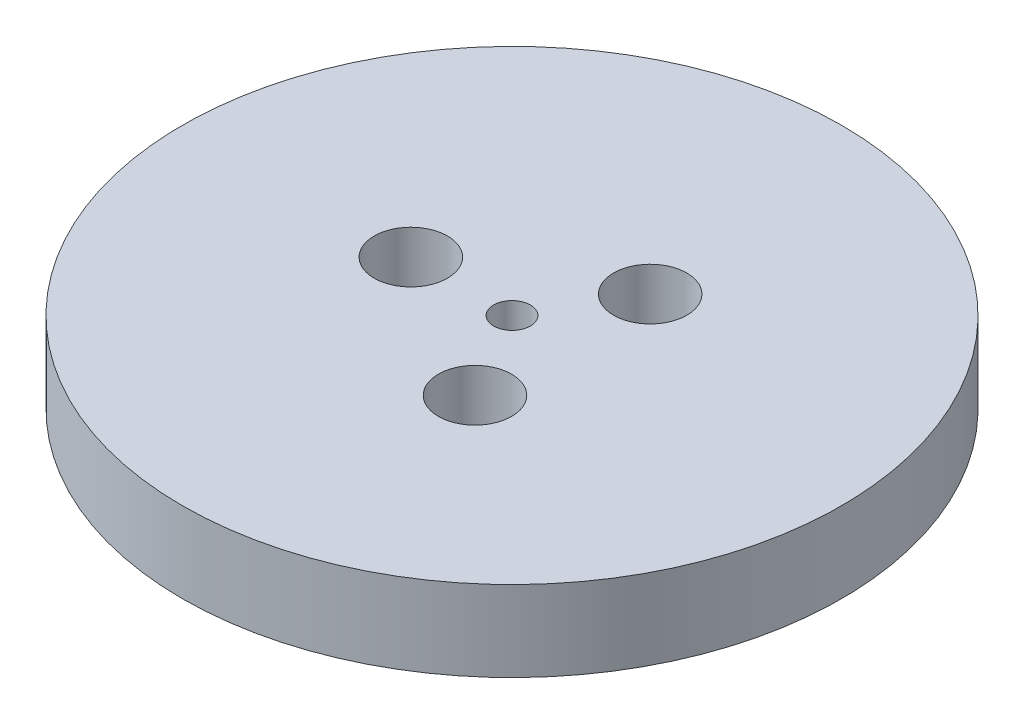
SolidWorks part; units mm, degrees
ref_plane "Front Plane" through (0, 0, 0) normal (0, 0, 1) x (1, 0, 0)
ref_plane "Top Plane" through (0, 0, 0) normal (0, 1, 0) x (1, 0, 0)
ref_plane "Right Plane" through (0, 0, 0) normal (1, 0, 0) x (0, 0, -1)
sketch "Sketch1" plane through (0, 0, 0) normal (0, 1, 0) x (1, 0, 0)
  circle A0 centre (0, 0) radius 90
  dimension "FLANGE_OD" = 180
extrude "Boss-Extrude1" add sketch "Sketch1" along normal blind 22
sketch "Sketch2" plane through (0, 0, 0) normal (0, 1, 0) x (1, 0, 0)
  circle A0 centre (0, 0) radius 5
  dimension "BORE_D" = 10
extrude "Cut-Extrude1" cut sketch "Sketch2" along normal through all
sketch "Sketch3" plane through (0, 22, 0) normal (0, 1, 0) x (1, 0, 0)
  circle A0 centre (0, 0) radius 27.624 construction
  circle A1 centre (-27.624, 0) radius 10
  dimension "BOLT_D" = 20
  dimension "BOLT_PCD" = 55.248
extrude "Cut-Extrude2" cut sketch "Sketch3" against normal blind 19.8338
pattern_circular "CirPattern1" count 3 over 360 about axis through (0, 0, 0) along (0, 1, 0) of "Cut-Extrude2"
